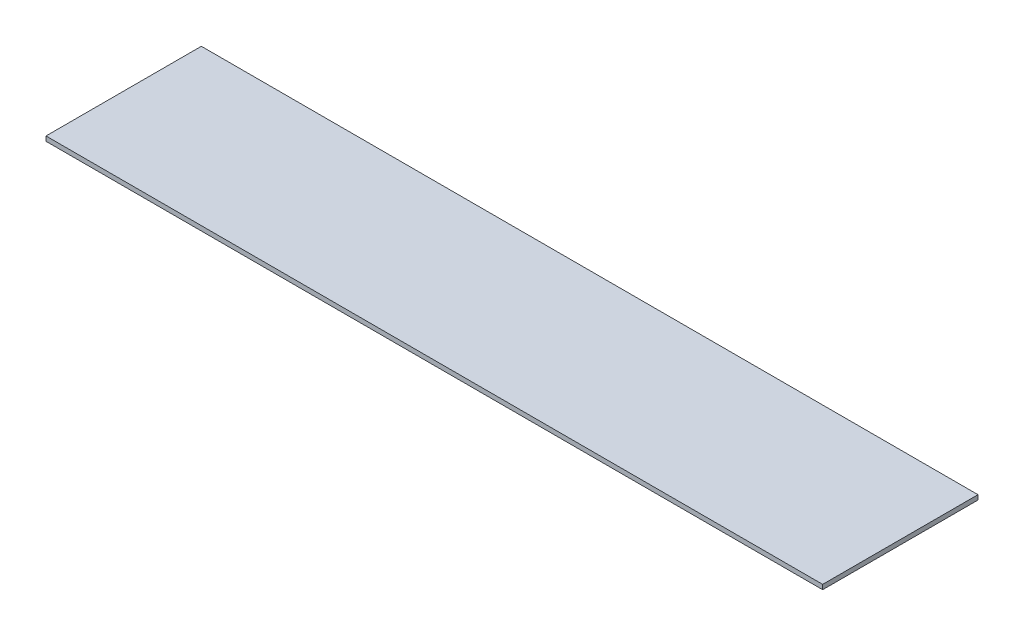
SolidWorks part; units mm, degrees
material "Default"
ref_plane "Front Plane" through (0, 0, 0) normal (0, 0, 1) x (1, 0, 0)
ref_plane "Top Plane" through (0, 0, 0) normal (0, 1, 0) x (1, 0, 0)
ref_plane "Right Plane" through (0, 0, 0) normal (1, 0, 0) x (0, 0, -1)
sketch "Sketch1" plane through (0, 0, 0) normal (0, 1, 0) x (1, 0, 0)
  line L5 (0, 0) -> (-125, 0)
  line L6 (0, 0) -> (0, 25)
  line L7 (0, 25) -> (-125, 25)
  line L8 (-125, 0) -> (-125, 25)
  dimension "D1" = 125
  dimension "D2" = 25
extrude "Boss-Extrude1" add sketch "Sketch1" along normal blind 0.75
ref_axis "Axis1" through (0, 0.7875, 0) along (0, -1, 0)
